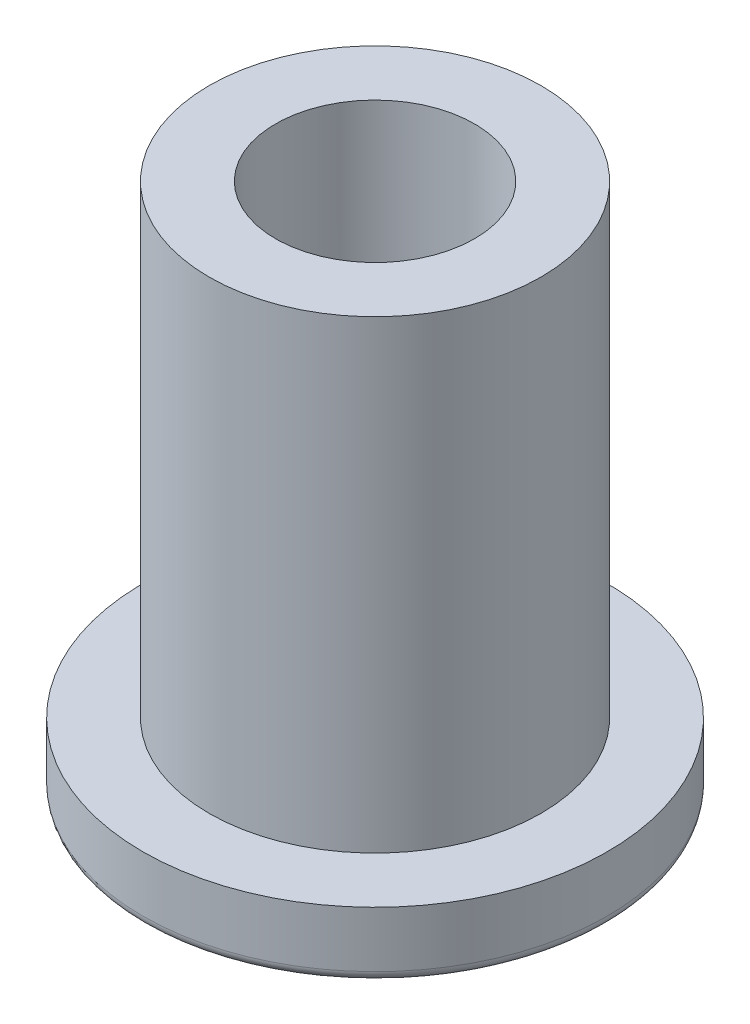
SolidWorks part; units mm, degrees
material "PET"
ref_plane "Front Plane" through (0, 0, 0) normal (0, 0, 1) x (1, 0, 0)
ref_plane "Top Plane" through (0, 0, 0) normal (0, 1, 0) x (1, 0, 0)
ref_plane "Right Plane" through (0, 0, 0) normal (1, 0, 0) x (0, 0, -1)
ref_axis "X-Axis" through (-88.99, 0, 0) along (1, 0, 0)
ref_axis "Y-Axis" through (0, 55, 0) along (0, -1, 0)
ref_axis "Z-Axis" through (0, 0, -88.99) along (0, 0, 1)
sketch "Sketch1" plane through (0, 0, 0) normal (0, 1, 0) x (1, 0, 0)
  circle A0 centre (0, 0) radius 5.5562
  dimension "D1" = 11.1125
extrude "Boss-Extrude1" add sketch "Sketch1" along normal blind 1.5875
ref_plane "Plane1" through (0, 1.5875, 0) normal (0, 1, 0) x (1, 0, 0)
sketch "Sketch2" plane through (0, 1.5875, 0) normal (0, 1, 0) x (1, 0, 0)
  circle A0 centre (0, 0) radius 3.9688
  dimension "D1" = 7.9375
extrude "Extrude-Thin1" add sketch "Sketch2" along normal blind 11.1125 thin thin type one direction reverse wall 1.5875
fillet "Fillet1" radius 0.254 1 edges at (0, 0, 5.5562)
